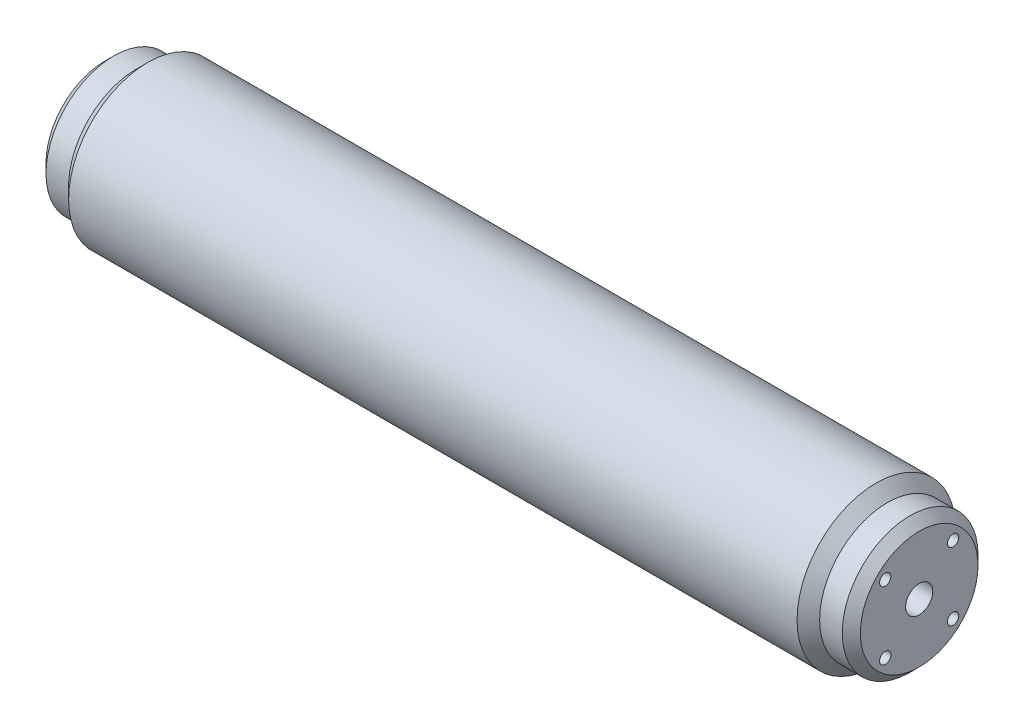
SolidWorks part; units mm, degrees
material "6061 Alloy"
ref_plane "Front Plane" through (0, 0, 0) normal (0, 0, 1) x (1, 0, 0)
ref_plane "Top Plane" through (0, 0, 0) normal (0, 1, 0) x (1, 0, 0)
ref_plane "Right Plane" through (0, 0, 0) normal (1, 0, 0) x (0, 0, -1)
sketch "Sketch1" plane through (0, 0, 0) normal (1, 0, 0) x (0, 0, -1)
  circle A0 centre (0, 0) radius 17.5
  dimension "D1" = 35
extrude "Boss-Extrude1" add sketch "Sketch1" along normal mid plane 160
sketch "Sketch7" plane through (-80, 0, 0) normal (-1, 0, 0) x (0, 0, 1)
  circle A0 centre (0, 0) radius 15
  dimension "D1" = 30
extrude "Boss-Extrude2" add sketch "Sketch7" along normal blind 10
mirror "Mirror3" about plane through (0, 0, 0) normal (1, 0, 0) of "Boss-Extrude2"
chamfer "Chamfer1" distance 3 angle 45 2 edges at (80, 0, 15) (-80, 0, 15)
chamfer "Chamfer2" distance 2 angle 45 2 edges at (-90, 0, 15) (90, 0, 15)
hole_wizard "M3 Tapped Hole1" positions "Sketch8" profile "Sketch9" tap size "M3" standard "GB"
sketch "Sketch8" plane through (-90, 0, 0) normal (-1, 0, 0) x (0, 0, 1)
  line L0 (0, -55) -> (0, 55) construction
  line L1 (55, 0) -> (-55, 0) construction
  point P0 (-7.5, 7.5)
  point P6 (7.5, 7.5)
  point P9 (7.5, -7.5)
  point P10 (-7.5, -7.5)
  dimension "D1" = 15
  dimension "D2" = 15
sketch "Sketch9" plane through (-90, 7.5, -7.5) normal (0, 1, 0) x (0, 0, 1)
  line L0 (0, 0) -> (0, 9.2511)
  line L1 (0, 9.2511) -> (1.25, 8.5)
  line L2 (1.25, 8.5) -> (1.25, 0)
  line L5 (1.25, 0) -> (0, 0)
  line L10 (0, 9.2511) -> (-1.25, 8.5) construction
  line L11 (0, -6.35) -> (0, 107.95) construction
  dimension "Tap Drill Dia." = 2.5
  dimension "Tap Drill Depth" = 8.5
  dimension "Drill Angle" = 118
cosmetic thread "Hole Thread1"
cosmetic thread "Hole Thread2"
cosmetic thread "Hole Thread3"
cosmetic thread "Hole Thread4"
hole_wizard "Ø6.0mm Dowel Hole1" positions "Sketch10" profile "Sketch11" hole size "Ø6.0" standard "GB"
sketch "Sketch10" plane through (-90, 0, 0) normal (-1, 0, 0) x (0, 0, 1)
  point P0 (0, 0)
sketch "Sketch11" plane through (-90, 0, 0) normal (0, 1, 0) x (0, 0, 1)
  line L0 (0, 0) -> (0, 10.3026)
  line L1 (0, 10.3026) -> (3, 8.5)
  line L2 (3, 8.5) -> (3, 0)
  line L5 (3, 0) -> (0, 0)
  line L10 (0, 10.3026) -> (-3, 8.5) construction
  line L11 (0, -6.35) -> (0, 107.95) construction
  dimension "Hole Dia." = 6
  dimension "Hole Depth" = 8.5
  dimension "Drill Angle" = 118
mirror "Mirror4" about plane through (0, 0, 0) normal (1, 0, 0) of "Ø6.0mm Dowel Hole1", "M3 Tapped Hole1"
cosmetic thread "Hole Thread5"
cosmetic thread "Hole Thread6"
cosmetic thread "Hole Thread7"
cosmetic thread "Hole Thread8"
